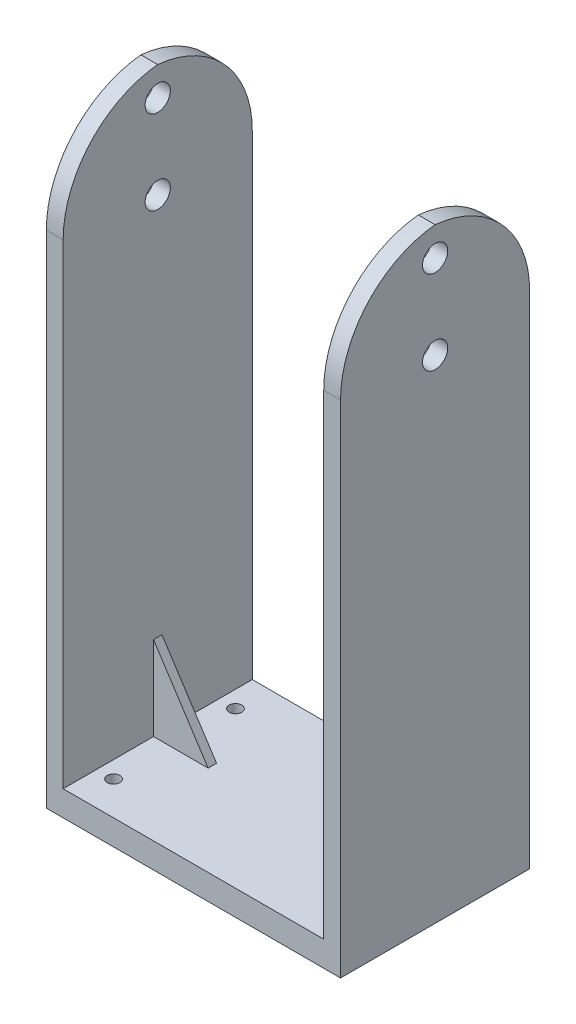
SolidWorks part; units mm, degrees
ref_plane "Front Plane" through (0, 0, 0) normal (0, 0, 1) x (1, 0, 0)
ref_plane "Top Plane" through (0, 0, 0) normal (0, 1, 0) x (1, 0, 0)
ref_plane "Right Plane" through (0, 0, 0) normal (1, 0, 0) x (0, 0, -1)
sketch "Sketch1" plane through (148.742, 0, 254.0578) normal (0, -1, 0) x (1, 0, 0)
  line L1 (-21.8688, 103.4949) -> (48.1312, 103.4949)
  line L2 (-21.8688, 103.4949) -> (-21.8688, 58.4949)
  line L3 (-21.8688, 58.4949) -> (48.1312, 58.4949)
  line L4 (48.1312, 103.4949) -> (48.1312, 58.4949)
  dimension "D1" = 70
  dimension "D2" = 45
extrude "Boss-Extrude1" add sketch "Sketch1" against normal blind 6
sketch "Sketch2" plane through (0, 0, 0) normal (0, 1, 0) x (-1, 0, 0)
  line L0 (-126.8732, 335.0527) -> (-196.8732, 335.0527) construction
  line L1 (-126.8732, 357.5527) -> (-126.8732, 312.5527) construction
  line L2 (-196.8732, 312.5527) -> (-196.8732, 357.5527) construction
  line L3 (-161.8732, 357.5527) -> (-161.8732, 312.5527) construction
  line L4 (-196.8732, 357.5527) -> (-126.8732, 357.5527) construction
  line L5 (-126.8732, 312.5527) -> (-196.8732, 312.5527) construction
sketch "Sketch4" plane through (0, 6, 0) normal (0, 1, 0) x (-1, 0, 0)
  line L0 (-188.8732, 349.5527) -> (-134.8732, 349.5527) construction
  line L1 (-134.8732, 349.5527) -> (-134.8732, 320.5527) construction
  line L2 (-134.8732, 320.5527) -> (-188.8732, 320.5527) construction
  line L3 (-188.8732, 320.5527) -> (-188.8732, 349.5527) construction
  circle A0 centre (-188.8732, 320.5527) radius 1.5 construction
  circle A1 centre (-188.8732, 349.5527) radius 1.5 construction
  circle A2 centre (-134.8732, 320.5527) radius 1.5 construction
  circle A3 centre (-134.8732, 349.5527) radius 1.5 construction
  circle A4 centre (-188.8732, 320.5527) radius 1.5
  circle A5 centre (-188.8732, 349.5527) radius 1.5
  circle A6 centre (-134.8732, 320.5527) radius 1.5
  circle A7 centre (-134.8732, 349.5527) radius 1.5
  dimension "D3" = 3
  dimension "D1" = 54
  dimension "D2" = 29
extrude "Cut-Extrude1" cut sketch "Sketch4" against normal up to next
sketch "Sketch5" plane through (0, 6, 0) normal (0, -1, 0) x (-1, 0, 0)
  line L0 (-196.8732, -357.5527) -> (-126.8732, -357.5527) construction
  line L1 (-126.8732, -312.5527) -> (-130.8732, -312.5527)
  line L2 (-126.8732, -312.5527) -> (-126.8732, -357.5527)
  line L3 (-126.8732, -357.5527) -> (-130.8732, -357.5527)
  line L4 (-130.8732, -312.5527) -> (-130.8732, -357.5527)
  line L5 (-126.8732, -312.5527) -> (-196.8732, -312.5527) construction
  dimension "D1" = 4
extrude "Boss-Extrude2" add sketch "Sketch5" against normal blind 138.11
sketch "Sketch6" plane through (126.8732, 0, 0) normal (-1, 0, 0) x (0, 0, 1)
  line L0 (335.0527, 0) -> (335.0527, 144.11) construction
  line L1 (357.5527, 0) -> (312.5527, 0) construction
  line L2 (357.5527, 144.11) -> (312.5527, 144.11) construction
  circle A0 centre (335.0527, 137.11) radius 3
  circle A1 centre (335.0527, 117.11) radius 3
  dimension "D2" = 4
  dimension "D3" = 6
  dimension "D1" = 20
extrude "Cut-Extrude2" cut sketch "Sketch6" against normal up to next
ref_plane "Plane1" through (161.8732, 0, 0) normal (1, 0, 0) x (0, 0, -1)
mirror "Mirror1" about plane through (161.8732, 0, 0) normal (1, 0, 0) of "Cut-Extrude2", "Boss-Extrude2"
fillet "Fillet1" radius 25 4 edges at (194.8732, 144.11, 357.5527) (128.8732, 144.11, 357.5527) (194.8732, 144.11, 312.5527) (128.8732, 144.11, 312.5527)
ref_plane "Plane2" through (0, 0, 335.0527) normal (0, 0, -1) x (-1, 0, 0)
sketch "Sketch8" plane through (0, 0, 335.0527) normal (0, 0, -1) x (-1, 0, 0)
  line L0 (-192.8732, 6) -> (-192.8732, 26)
  line L2 (-192.8732, 26) -> (-179.8732, 6)
  line L3 (-130.8732, 6) -> (-192.8732, 6) construction
  line L4 (-179.8732, 6) -> (-192.8732, 6)
  line L5 (-130.8732, 26) -> (-143.8732, 6)
  line L7 (-143.8732, 6) -> (-130.8732, 6)
  line L8 (-130.8732, 6) -> (-130.8732, 26)
  dimension "D1" = 20
  dimension "D2" = 13
extrude "Boss-Extrude3" add sketch "Sketch8" along normal blind 1 and the other way blind 1
